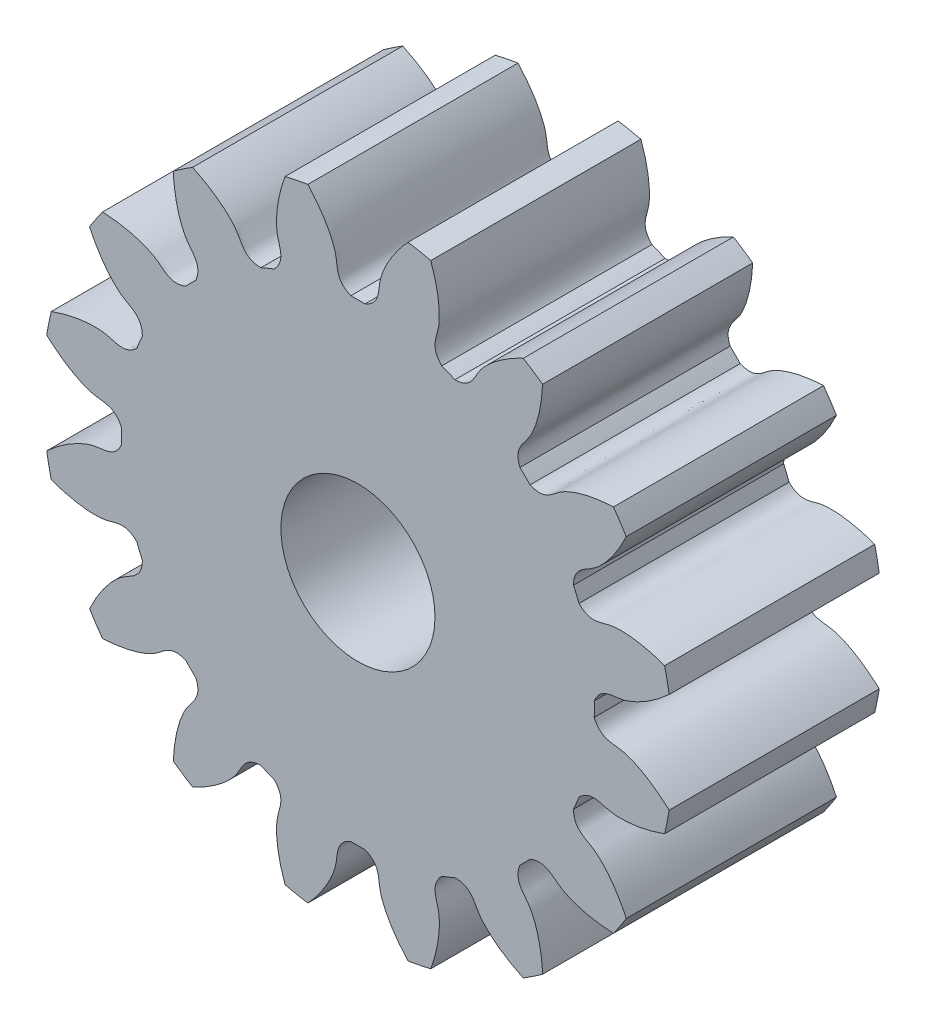
SolidWorks part; units mm, degrees
ref_plane "前视基准面" through (0, 0, 0) normal (0, 0, 1) x (1, 0, 0)
ref_plane "上视基准面" through (0, 0, 0) normal (0, 1, 0) x (1, 0, 0)
ref_plane "右视基准面" through (0, 0, 0) normal (1, 0, 0) x (0, 0, -1)
other "Configuration Table"
sketch "草图1" plane through (0, 0, 0) normal (0, 0, 1) x (1, 0, 0)
  circle A0 centre (0, 0) radius 4.5
extrude "凸台-拉伸1" add sketch "草图1" along normal blind 3
ref_axis "基准轴1" through (0, 0, 3) along (0, 0, -1)
sketch "草图2" plane through (0, 0, 0) normal (0, 0, 1) x (1, 0, 0)
  line L0 (0, 0) -> (0, 4.5) construction
  circle A0 centre (0, 0) radius 4.5 construction
  arc A1 (0.1017, 3.3735) -> (-0.1017, 3.3735) centre (0, 0) ccw
  arc A2 (1.5609, 5.0814) -> (-1.5609, 5.0814) centre (0, 0) ccw
  spline S0 degree 3 poles (0.1017, 3.3735) (0.3209, 3.4651) (0.2847, 3.6353) (0.3224, 3.7934) (0.3256, 3.8058) (0.3295, 3.8195) (0.334, 3.8346) (0.3394, 3.8511) (0.3455, 3.8688) (0.3526, 3.8879) (0.3605, 3.9082) (0.3695, 3.9297) (0.3794, 3.9524) (0.3905, 3.9763) (0.4027, 4.0013) (0.4161, 4.0274) (0.4307, 4.0545) (0.4466, 4.0827) (0.4638, 4.1118) (0.4823, 4.1419) (0.5023, 4.1728) (0.5238, 4.2046) (0.5467, 4.2372) (0.5712, 4.2705) (0.5973, 4.3045) (0.6249, 4.3392) (0.6543, 4.3744) (0.6853, 4.4102) (0.718, 4.4465) (0.7524, 4.4833) (0.7887, 4.5204) (0.8267, 4.5578) (0.8666, 4.5955) (0.9084, 4.6334) (0.952, 4.6715) (0.9975, 4.7096) (1.045, 4.7478) (1.0944, 4.7859) (1.1457, 4.8239) (1.1991, 4.8618) (1.2544, 4.8994) (1.3117, 4.9367) (1.3711, 4.9737) (1.4537, 5.023) (1.5175, 5.0584) (1.5609, 5.0814) knots 0 0 0 0 0.200958 0.205848 0.21139 0.217584 0.224431 0.231929 0.240079 0.248881 0.258335 0.268441 0.2792 0.29061 0.302672 0.315386 0.328753 0.342771 0.357441 0.372764 0.388738 0.405364 0.422643 0.440573 0.459155 0.47839 0.498276 0.518814 0.540005 0.561847 0.584342 0.607488 0.631287 0.655737 0.68084 0.706594 0.733001 0.760059 0.78777 0.816132 0.845147 0.874814 0.905132 0.936103 1 1 1 1
  spline S1 degree 3 poles (-0.1017, 3.3735) (-0.3209, 3.4651) (-0.2847, 3.6353) (-0.3224, 3.7934) (-0.3256, 3.8058) (-0.3295, 3.8195) (-0.334, 3.8346) (-0.3394, 3.8511) (-0.3455, 3.8688) (-0.3526, 3.8879) (-0.3605, 3.9082) (-0.3695, 3.9297) (-0.3794, 3.9524) (-0.3905, 3.9763) (-0.4027, 4.0013) (-0.4161, 4.0274) (-0.4307, 4.0545) (-0.4466, 4.0827) (-0.4638, 4.1118) (-0.4823, 4.1419) (-0.5023, 4.1728) (-0.5238, 4.2046) (-0.5467, 4.2372) (-0.5712, 4.2705) (-0.5973, 4.3045) (-0.6249, 4.3392) (-0.6543, 4.3744) (-0.6853, 4.4102) (-0.718, 4.4465) (-0.7524, 4.4833) (-0.7887, 4.5204) (-0.8267, 4.5578) (-0.8666, 4.5955) (-0.9084, 4.6334) (-0.952, 4.6715) (-0.9975, 4.7096) (-1.045, 4.7478) (-1.0944, 4.7859) (-1.1457, 4.8239) (-1.1991, 4.8618) (-1.2544, 4.8994) (-1.3117, 4.9367) (-1.3711, 4.9737) (-1.4537, 5.023) (-1.5175, 5.0584) (-1.5609, 5.0814) knots 0 0 0 0 0.200958 0.205848 0.21139 0.217584 0.224431 0.231929 0.240079 0.248881 0.258335 0.268441 0.2792 0.29061 0.302672 0.315386 0.328753 0.342771 0.357441 0.372764 0.388738 0.405364 0.422643 0.440573 0.459155 0.47839 0.498276 0.518814 0.540005 0.561847 0.584342 0.607488 0.631287 0.655737 0.68084 0.706594 0.733001 0.760059 0.78777 0.816132 0.845147 0.874814 0.905132 0.936103 1 1 1 1
extrude "切除-拉伸1" cut sketch "草图2" along normal through all
pattern_circular "阵列(圆周)1" count 16 every 22.5 about axis through (0, 0, 3) along (0, 0, -1) of "切除-拉伸1"
sketch "草图3" plane through (0, 0, 0) normal (0, 0, 1) x (1, 0, 0)
  circle A0 centre (0, 0) radius 4 construction
  dimension "Dn" = 8
sketch "草图4" plane through (0, 0, 3) normal (0, 0, 1) x (1, 0, 0)
  circle A0 centre (0, 0) radius 1.1
  dimension "D1" = 2.2
extrude "切除-拉伸2" cut sketch "草图4" against normal blind 10
